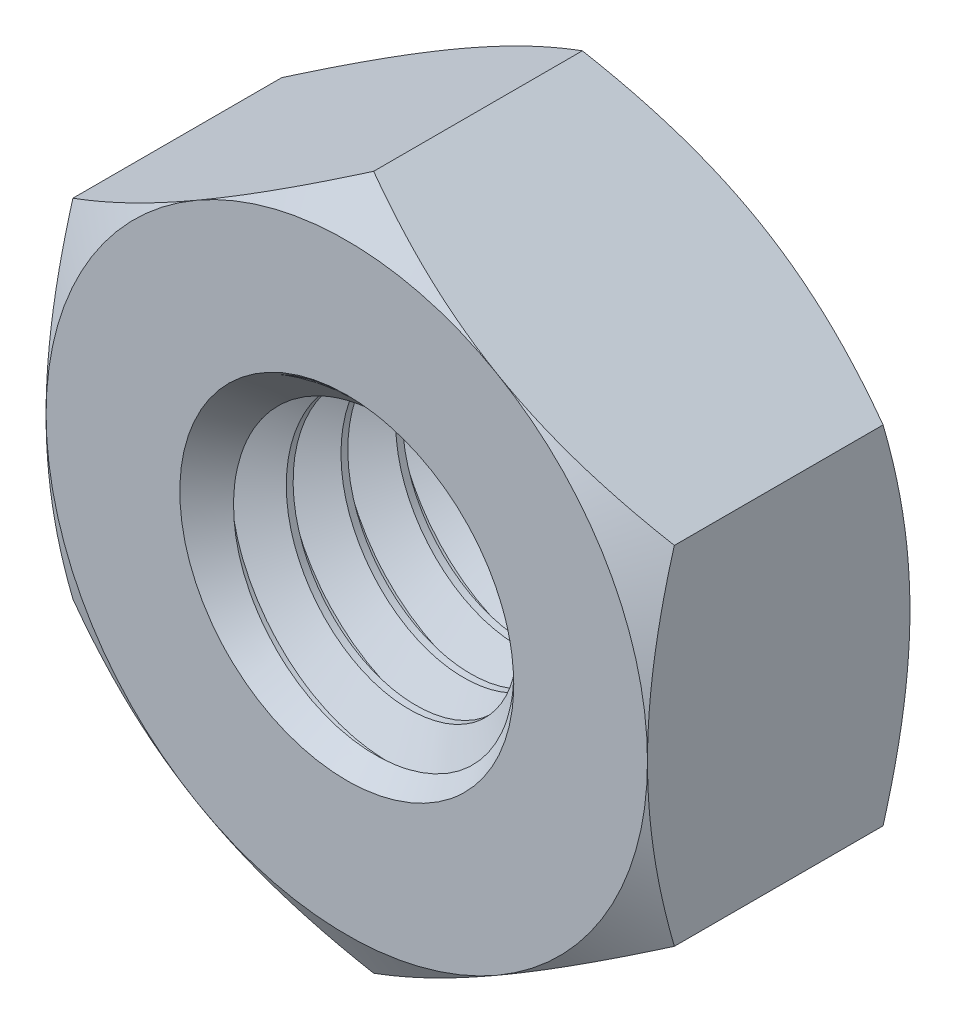
SolidWorks part; units mm, degrees
ref_plane "Front Plane" through (0, 0, 0) normal (0, 0, 1) x (1, 0, 0)
ref_plane "Top Plane" through (0, 0, 0) normal (0, 1, 0) x (1, 0, 0)
ref_plane "Right Plane" through (0, 0, 0) normal (1, 0, 0) x (0, 0, -1)
sketch "Sketch1" plane through (0, 0, 0) normal (1, 0, 0) x (0, 0, -1)
  line L0 (-1.2, 0) -> (1.2, 0) construction
  line L1 (-1.2, -2.75) -> (-1.2, 2.75) construction
  line L2 (1.2, -2.75) -> (1.2, 2.75) construction
  line L3 (-1.2, -1.5) -> (-1.2, 1.5) construction
  line L4 (-1.6688, 1.5541) -> (-1.4188, 1.1211) construction
  line L5 (-1.4188, 1.1211) -> (-1.1688, 1.5541) construction
  line L6 (-1.1688, 1.5541) -> (-1.6688, 1.5541) construction
  line L7 (-1.6531, 1.5271) -> (-1.1844, 1.5271) construction
  line L8 (-1.6375, 1.5) -> (-1.2, 1.5) construction
  line L9 (-1.45, 1.1752) -> (-1.3875, 1.1752) construction
  line L10 (-1.4188, 1.1752) -> (-1.4188, 1.1211) construction
  line L11 (-1.4188, 1.5541) -> (-1.4188, 1.5) construction
  point P4 (0, 0)
  point P7 (-1.2, 0)
  point P11 (1.2, 0)
  point P14 (-1.2, 0)
  point P26 (-1.4188, 1.5271)
  point P27 (-1.2, -1.5)
  dimension "Height" = 2.4
  dimension "Width" = 5.5
  dimension "Thread OD" = 3
  dimension "D1" = 60
  dimension "Pitch" = 0.5
  dimension "D2" = 0.0625
sketch "Sketch2" plane through (0, 0, 0) normal (0, 0, 1) x (1, 0, 0)
  line L1 (0, 3.1754) -> (-2.75, 1.5877)
  line L2 (-2.75, 1.5877) -> (-2.75, -1.5877)
  line L3 (-2.75, -1.5877) -> (0, -3.1754)
  line L4 (0, -3.1754) -> (2.75, -1.5877)
  line L5 (2.75, -1.5877) -> (2.75, 1.5877)
  line L6 (2.75, 1.5877) -> (0, 3.1754)
  circle A0 centre (0, 0) radius 2.75 construction
  circle A1 centre (0, 0) radius 1.5
extrude "Boss-Extrude1" add sketch "Sketch2" along normal up to vertex (1.2 mm away) and the other way up to vertex (1.2 mm away) up to point (0, -2.75, 1.2) other way up to point (0, -2.75, -1.2)
sketch "Sketch3" plane through (0, 0, 1.2) normal (0, 0, 1) x (1, 0, 0)
  circle A0 centre (0, 0) radius 2.75
extrude "Cut-Extrude1" cut sketch "Sketch3" against normal through all draft 60 flip side to cut
mirror "Mirror1" about plane through (0, 0, 0) normal (0, 0, 1) of "Cut-Extrude1"
ref_axis "Center Axis 1" through (0, 0, -10.9016) along (0, 0, 1)
ref_plane "Contact Plane 1" through (0, 0, 1.2) normal (0, 0, 1) x (1, 0, 0)
ref_plane "Contact Plane 2" through (0, 0, -1.2) normal (0, 0, -1) x (-1, 0, 0)
sketch "Sketch4" plane through (0, 0, 0) normal (1, 0, 0) x (0, 0, -1)
  line L1 (-1.6531, 1.5271) -> (-1.45, 1.1752)
  line L2 (-1.45, 1.1752) -> (-1.3875, 1.1752)
  line L3 (-1.3875, 1.1752) -> (-1.1844, 1.5271)
  line L4 (-1.6531, 1.5271) -> (-1.1844, 1.5271) construction
  line L5 (-1.6531, 1.5271) -> (-1.1844, 1.5271)
sketch "Sketch5" plane through (0, 0, 1.2) normal (0, 0, 1) x (1, 0, 0)
  circle A0 centre (0, 0) radius 1.5 construction
  circle A1 centre (0, 0) radius 1.5
curve "Helix/Spiral1" pitch 0.5 height 2.9 radius 1.5 centre (0, 0, 1.2) axis (0, 0, -1) start towards (0, 1, 0)
sweep "Sweep1" add profiles "Sketch4" path "Helix/Spiral1"
sketch "Sketch6" plane through (0, 0, 1.2) normal (0, 0, 1) x (1, 0, 0)
  circle A1 centre (0, 0) radius 1.5271
extrude "Cut-Extrude2" cut sketch "Sketch6" along normal through all and the other way through all draft 45
sketch "Sketch7" plane through (0, 0, -1.2) normal (0, 0, -1) x (-1, 0, 0)
  circle A1 centre (0, 0) radius 1.5271
  circle A2 centre (0, 0) radius 1.5271
  dimension "D1" = 0
extrude "Cut-Extrude3" cut sketch "Sketch7" along normal through all and the other way through all draft 45
equation "\"D2@Sketch1\"=\"Pitch@Sketch1\"/8"
equation "\"D4@Helix/Spiral1\"=\"Pitch@Sketch1\""
equation "\"D3@Helix/Spiral1\"=\"Height@Sketch1\"+\"Pitch@Sketch1\""
